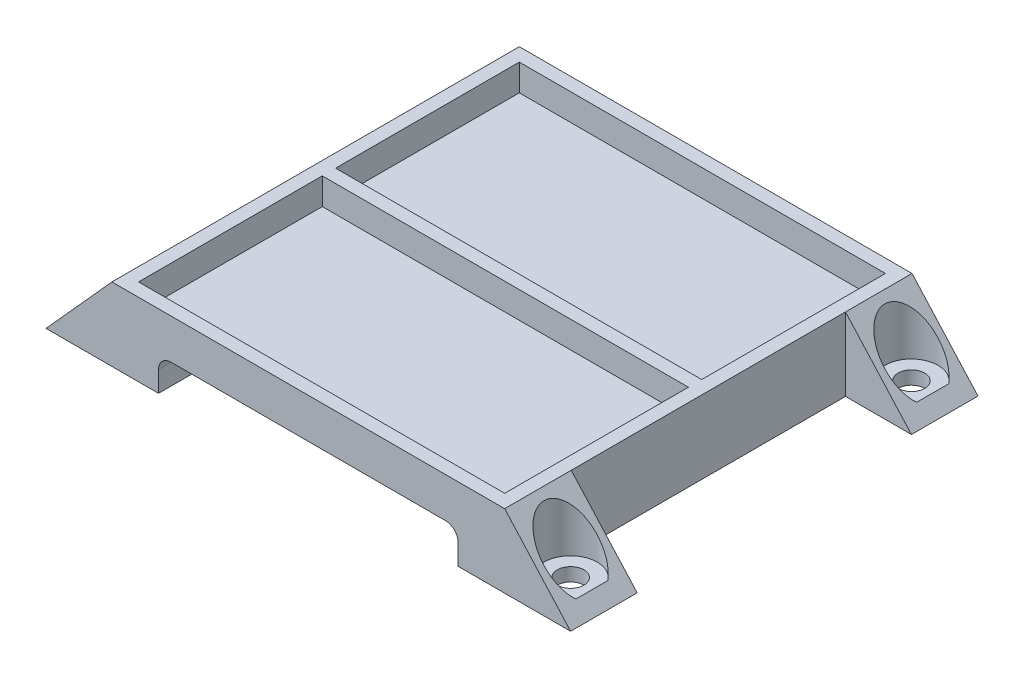
SolidWorks part; units mm, degrees
material "ABS"
ref_plane "Front Plane" through (0, 0, 0) normal (0, 0, 1) x (1, 0, 0)
ref_plane "Top Plane" through (0, 0, 0) normal (0, 1, 0) x (1, 0, 0)
ref_plane "Right Plane" through (0, 0, 0) normal (1, 0, 0) x (0, 0, -1)
sketch "Sketch1" plane through (0, 0, 0) normal (0, 1, 0) x (1, 0, 0)
  line L1 (-34.925, 17.526) -> (34.925, 17.526)
  line L2 (-34.925, 17.526) -> (-34.925, -17.526)
  line L3 (-34.925, -17.526) -> (34.925, -17.526)
  line L4 (34.925, 17.526) -> (34.925, -17.526)
  line L5 (-34.925, 17.526) -> (34.925, -17.526) construction
  line L6 (-34.925, -17.526) -> (34.925, 17.526) construction
  line L7 (-37.465, 20.066) -> (37.465, 20.066)
  line L8 (-37.465, 20.066) -> (-37.465, -20.066)
  line L9 (-37.465, -20.066) -> (37.465, -20.066)
  line L10 (37.465, 20.066) -> (37.465, -20.066)
  line L11 (-37.465, 20.066) -> (37.465, -20.066) construction
  line L12 (-37.465, -20.066) -> (37.465, 20.066) construction
  line L13 (-34.925, 20.066) -> (34.925, 20.066)
  line L14 (-34.925, 20.066) -> (-34.925, 55.118)
  line L15 (-34.925, 55.118) -> (34.925, 55.118)
  line L16 (34.925, 20.066) -> (34.925, 55.118)
  line L17 (-37.465, 20.066) -> (37.465, 20.066)
  line L18 (-37.465, 20.066) -> (-37.465, 57.658)
  line L19 (-37.465, 57.658) -> (37.465, 57.658)
  line L20 (37.465, 20.066) -> (37.465, 57.658)
  point P0 (0, 0)
  point P6 (0, 0)
  dimension "D1" = 69.85
  dimension "D2" = 35.052
  dimension "D3" = 2.54
  dimension "D4" = 2.54
  dimension "D5" = 2.54
  dimension "D6" = 35.052
extrude "Boss-Extrude1" add sketch "Sketch1" along normal blind 5.08 contours L7 L20 L19 L18 L14 L15 L16 | L10 L7 L8 L9 L1 L4 L3 L2 region at (-36.6267, 0, -38.862) region at (-36.195, 0, -19.216)
sketch "Sketch2" plane through (0, 0, 0) normal (0, -1, 0) x (1, 0, 0)
  line L1 (-37.465, -57.658) -> (37.465, -57.658)
  line L2 (-37.465, -57.658) -> (-37.465, 20.066)
  line L3 (-37.465, 20.066) -> (37.465, 20.066)
  line L4 (37.465, -57.658) -> (37.465, 20.066)
extrude "Boss-Extrude2" add sketch "Sketch2" along normal blind 2.54
sketch "Sketch3" plane through (0, -2.54, 0) normal (0, -1, 0) x (-1, 0, 0)
  line L0 (37.465, 57.658) -> (-37.465, 57.658) construction
  line L1 (-37.465, -20.066) -> (-28.575, -20.066)
  line L2 (-37.465, -20.066) -> (-37.465, 57.658)
  line L3 (-37.465, 57.658) -> (-28.575, 57.658)
  line L4 (-28.575, -20.066) -> (-28.575, 57.658)
  line L6 (37.465, -20.066) -> (28.575, -20.066)
  line L7 (37.465, -20.066) -> (37.465, 57.658)
  line L8 (37.465, 57.658) -> (28.575, 57.658)
  line L9 (28.575, -20.066) -> (28.575, 57.658)
  dimension "D1" = 8.89
  dimension "D2" = 8.89
extrude "Boss-Extrude3" add sketch "Sketch3" along normal blind 6.35
sketch "Sketch5" plane through (37.465, 0, 0) normal (1, 0, 0) x (0, 0, -1)
  line L0 (-20.066, 5.08) -> (57.658, 5.08) construction
  line L1 (57.658, -8.89) -> (44.958, -8.89)
  line L2 (57.658, -8.89) -> (57.658, 5.08)
  line L3 (57.658, 5.08) -> (44.958, 5.08)
  line L4 (44.958, -8.89) -> (44.958, 5.08)
  line L6 (-20.066, -8.89) -> (-7.366, -8.89)
  line L7 (-20.066, -8.89) -> (-20.066, 5.08)
  line L8 (-20.066, 5.08) -> (-7.366, 5.08)
  line L9 (-7.366, -8.89) -> (-7.366, 5.08)
  dimension "D1" = 12.7
  dimension "D2" = 12.7
extrude "Boss-Extrude5" add sketch "Sketch5" along normal blind 12.7
sketch "Sketch6" plane through (-37.465, 0, 0) normal (-1, 0, 0) x (0, 0, 1)
  line L0 (20.066, -8.89) -> (-57.658, -8.89) construction
  line L1 (-57.658, 5.08) -> (-44.958, 5.08)
  line L2 (-57.658, 5.08) -> (-57.658, -8.89)
  line L3 (-57.658, -8.89) -> (-44.958, -8.89)
  line L4 (-44.958, 5.08) -> (-44.958, -8.89)
  line L5 (20.066, 5.08) -> (-57.658, 5.08) construction
  line L6 (20.066, -8.89) -> (7.366, -8.89)
  line L7 (20.066, -8.89) -> (20.066, 5.08)
  line L8 (20.066, 5.08) -> (7.366, 5.08)
  line L9 (7.366, -8.89) -> (7.366, 5.08)
  dimension "D1" = 12.7
  dimension "D2" = 12.7
extrude "Boss-Extrude6" add sketch "Sketch6" along normal blind 12.7
chamfer "Chamfer2" distance 12.7 angle 48 4 edges at (50.165, 5.08, 13.716) (50.165, 5.08, -51.308) (-50.165, 5.08, 13.716) (-50.165, 5.08, -51.308) first distance on face at (0, 5.08, -18.796)
sketch "Sketch7" plane through (0, -8.89, 0) normal (0, -1, 0) x (-1, 0, 0)
  line L0 (-50.0436, -20.066) -> (-28.575, -20.066) construction
  line L1 (-50.0436, -7.366) -> (-50.0436, -20.066) construction
  line L2 (50.0436, -7.366) -> (37.465, -7.366) construction
  line L3 (50.0436, -20.066) -> (50.0436, -7.366) construction
  line L4 (-50.0436, 57.658) -> (-50.0436, 44.958) construction
  line L5 (-28.575, 57.658) -> (-50.0436, 57.658) construction
  line L6 (50.0436, 57.658) -> (28.575, 57.658) construction
  line L7 (50.0436, 44.958) -> (50.0436, 57.658) construction
  circle A0 centre (-43.6936, 51.308) radius 2.54
  circle A1 centre (-43.6936, -13.716) radius 2.54
  circle A2 centre (43.6936, -13.716) radius 2.54
  circle A3 centre (43.6936, 51.308) radius 2.54
  dimension "D1" = 5.08
  dimension "D2" = 5.08
  dimension "D3" = 5.08
  dimension "D4" = 5.08
  dimension "D5" = 6.35
  dimension "D6" = 6.35
  dimension "D7" = 6.35
  dimension "D8" = 6.35
  dimension "D9" = 6.35
  dimension "D10" = 6.35
  dimension "D11" = 6.35
  dimension "D12" = 6.35
extrude "Cut-Extrude1" cut sketch "Sketch7" against normal through all
sketch "Sketch8" plane through (0, -8.89, 0) normal (0, -1, 0) x (-1, 0, 0)
  circle A0 centre (-43.6936, 51.308) radius 5.08
  circle A1 centre (-43.6936, -13.716) radius 5.08
  circle A2 centre (43.6936, -13.716) radius 5.08
  circle A3 centre (43.6936, 51.308) radius 5.08
  circle A4 centre (-43.6936, -13.716) radius 2.54 construction
  dimension "D1" = 10.16
  dimension "D2" = 10.16
  dimension "D3" = 10.16
  dimension "D4" = 10.16
extrude "Cut-Extrude2" cut sketch "Sketch8" against normal through all from offset 2.54 offset against normal yes
fillet "Fillet1" radius 2.38 2 edges at (-28.575, -2.54, -18.796) (28.575, -2.54, -18.796)
